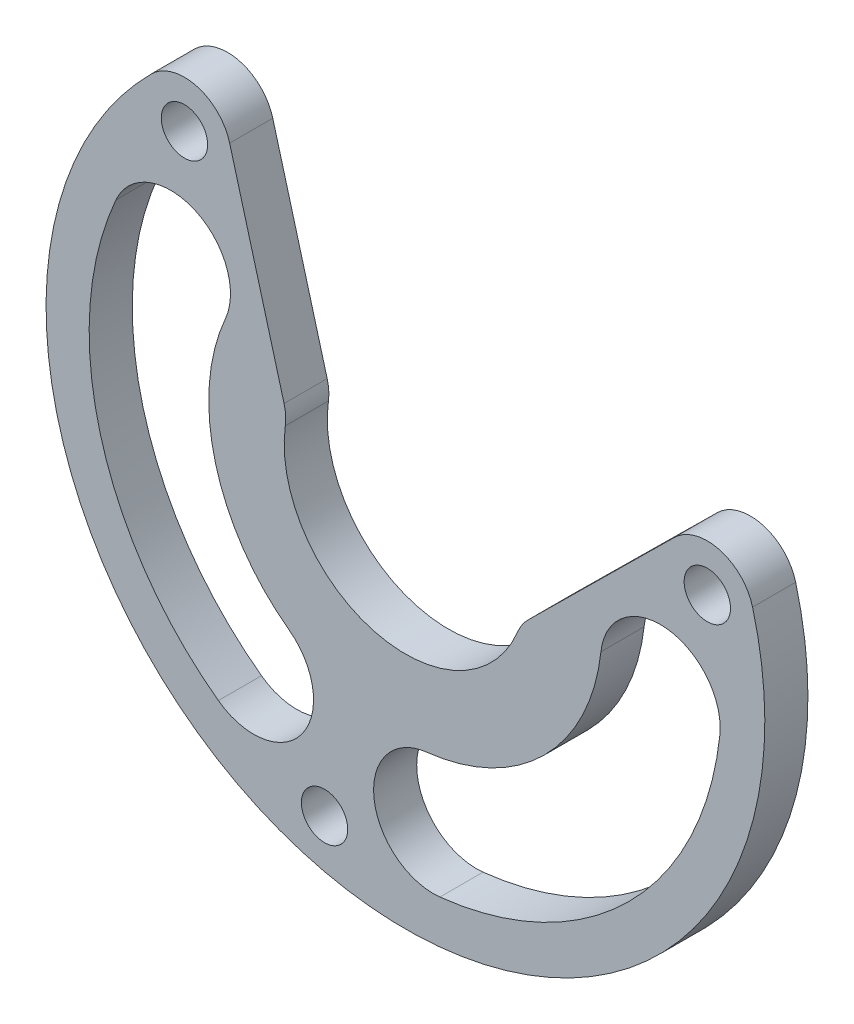
SolidWorks part; units mm, degrees
material "Thornel Mat VMA"
ref_plane "Front Plane" through (0, 0, 0) normal (0, 0, 1) x (1, 0, 0)
ref_plane "Top Plane" through (0, 0, 0) normal (0, 1, 0) x (1, 0, 0)
ref_plane "Right Plane" through (0, 0, 0) normal (1, 0, 0) x (0, 0, -1)
sketch "Sketch1" plane through (0, 0, 0) normal (0, 0, 1) x (1, 0, 0)
  line L0 (169.0712, 34.6) -> (155.4979, 21.1875)
  line L1 (132.8544, 27.2548) -> (127.8058, 45.657)
  line L2 (144.1169, 24) -> (173.1367, 52.6759) construction
  arc A0 (177.4669, 23.9998) -> (120.5529, 47.6) centre (144.1169, 24) ccw construction
  arc A1 (120.5349, 47.582) -> (176.3305, 32.6316) centre (144.1169, 24) ccw
  circle A2 centre (136.6111, -4.0118) radius 2.15 construction
  circle A3 centre (172.1287, 31.5058) radius 2.15 construction
  circle A4 centre (123.6108, 44.5061) radius 2.15 construction
  circle A5 centre (144.1169, 24) radius 11.25 construction
  arc A6 (146.1075, 5.8589) -> (147.3182, -5.1749) centre (146.7128, 0.342) ccw construction
  arc A7 (147.3182, -5.1749) -> (173.2918, 20.7987) centre (144.1169, 24) ccw construction
  arc A8 (146.1075, 5.8589) -> (162.258, 22.0094) centre (144.1169, 24) ccw construction
  arc A9 (173.2918, 20.7987) -> (162.258, 22.0094) centre (167.7749, 21.4041) ccw construction
  arc A10 (126.757, 0.3344) -> (133.3224, 9.2846) centre (130.0397, 4.8095) ccw construction
  arc A11 (117.25, 35.8151) -> (126.757, 0.3344) centre (144.1169, 24) ccw construction
  arc A12 (127.4109, 31.3467) -> (133.3224, 9.2846) centre (144.1169, 24) ccw construction
  arc A13 (127.4109, 31.3467) -> (117.25, 35.8151) centre (122.3305, 33.5809) ccw construction
  arc A14 (127.4109, 31.3467) -> (117.25, 35.8151) centre (122.3305, 33.5809) ccw
  arc A15 (127.4109, 31.3467) -> (133.3224, 9.2846) centre (144.1169, 24) ccw
  arc A16 (117.25, 35.8151) -> (126.757, 0.3344) centre (144.1169, 24) ccw
  arc A17 (126.757, 0.3344) -> (133.3224, 9.2846) centre (130.0397, 4.8095) ccw
  arc A18 (173.2918, 20.7987) -> (162.258, 22.0094) centre (167.7749, 21.4041) ccw
  arc A19 (146.1075, 5.8589) -> (162.258, 22.0094) centre (144.1169, 24) ccw
  arc A20 (147.3182, -5.1749) -> (173.2918, 20.7987) centre (144.1169, 24) ccw
  arc A21 (146.1075, 5.8589) -> (147.3182, -5.1749) centre (146.7128, 0.342) ccw
  arc A22 (132.9697, 25.5173) -> (154.5293, 19.7404) centre (144.1169, 24) ccw
  circle A23 centre (123.6108, 44.5061) radius 2.15
  circle A24 centre (172.1287, 31.5058) radius 2.15
  circle A25 centre (136.6111, -4.0118) radius 2.15
  arc A26 (176.3305, 32.6316) -> (169.0712, 34.6) centre (172.1287, 31.5058) ccw
  arc A27 (155.4979, 21.1875) -> (154.5293, 19.7404) centre (158.5554, 18.0933) ccw
  arc A28 (132.9697, 25.5173) -> (132.8544, 27.2548) centre (128.6594, 26.104) ccw
  arc A29 (120.5349, 47.582) -> (127.8058, 45.657) centre (123.6108, 44.5061) cw
  dimension "D1" = 10
extrude "Boss-Extrude1" add sketch "Sketch1" along normal blind 4
